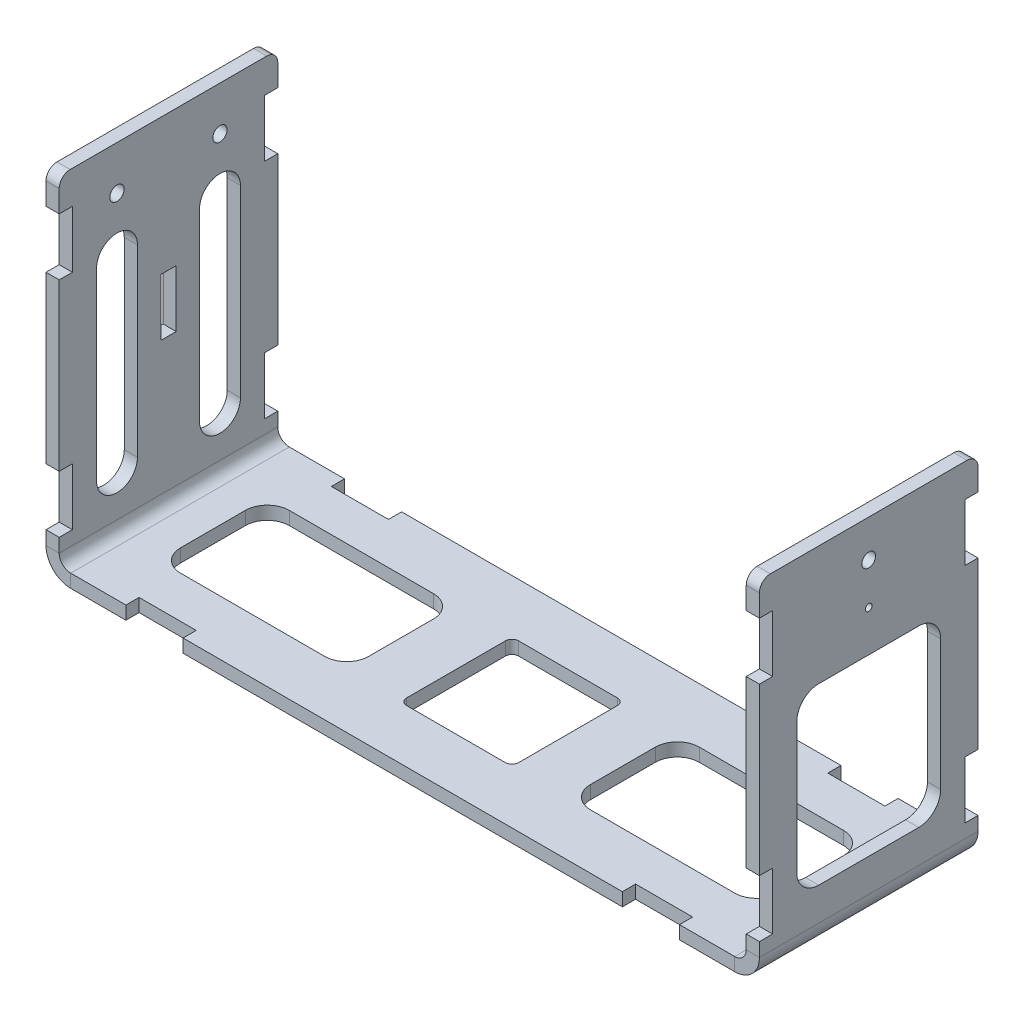
SolidWorks part; units mm, degrees
note: The reader was unsure of these and kept them because the rebuilt part matched: bend radius of "Base-Flange1", "BaseBend1", "BaseBend2".
ref_plane "Front Plane" through (0, 0, 0) normal (0, 0, 1) x (1, 0, 0)
ref_plane "Top Plane" through (0, 0, 0) normal (0, 1, 0) x (1, 0, 0)
ref_plane "Right Plane" through (0, 0, 0) normal (1, 0, 0) x (0, 0, -1)
sketch "Sketch1" plane through (0, 0, 0) normal (0, 0, 1) x (1, 0, 0)
  line L0 (79.4411, 0) -> (-79.4411, 0)
  line L1 (-79.4411, 0) -> (-79.4411, 78.232)
  line L2 (0, -1000) -> (0, 49000) construction
  line L3 (79.4411, 0) -> (79.4411, 78.232)
  line L4 (0, 78.232) -> (-38.1661, 40.0659) construction
  line L5 (-1000, 78.232) -> (49000, 78.232) construction
  line L6 (-66.7411, -930.7018) -> (-66.7411, 49069.2982) construction
  circle A0 centre (0, 78.232) radius 25.4 construction
  circle A1 centre (-38.1661, 40.0659) radius 28.575 construction
  circle A2 centre (0, 78.232) radius 29.21 construction
  point P7 (0, 0)
  dimension "D1" = 50.8
  dimension "D2" = 57.15
  dimension "D4" = 45
  dimension "D6" = 12.7
base flange "Base-Flange1" sketch "Sketch1" end condition mid plane depth 50.546 reverse direction no thickness 3.048 reverse thickness direction yes bend radius 2.667
bend "BaseBend1" bend radius 2.667 bend angle 90 parameters "D5"=1
bend "BaseBend2" bend radius 2.667 bend angle 90 parameters "D5"=2
sketch "Sketch6" plane through (0, 0, 0) normal (0, 1, 0) x (1, 0, 0)
  line L0 (76.7741, 25.273) -> (-76.7741, 25.273) construction
  line L1 (-64.008, 25.273) -> (-50.8, 25.273)
  line L2 (-64.008, 25.273) -> (-64.008, 22.225)
  line L3 (-64.008, 22.225) -> (-50.8, 22.225)
  line L4 (-50.8, 25.273) -> (-50.8, 22.225)
  line L5 (76.7741, -25.273) -> (-76.7741, -25.273) construction
  line L6 (-64.008, -25.273) -> (-50.8, -25.273)
  line L7 (-64.008, -25.273) -> (-64.008, -22.225)
  line L8 (-64.008, -22.225) -> (-50.8, -22.225)
  line L9 (-50.8, -25.273) -> (-50.8, -22.225)
  line L10 (-1000, 0) -> (49000, 0) construction
  line L11 (0, -1000) -> (0, 49000) construction
  line L24 (50.8, -25.273) -> (50.8, -22.225)
  line L25 (64.008, -22.225) -> (50.8, -22.225)
  line L26 (64.008, -25.273) -> (64.008, -22.225)
  line L27 (64.008, -25.273) -> (50.8, -25.273)
  line L28 (50.8, 25.273) -> (50.8, 22.225)
  line L29 (64.008, 22.225) -> (50.8, 22.225)
  line L30 (64.008, 25.273) -> (64.008, 22.225)
  line L31 (64.008, 25.273) -> (50.8, 25.273)
  dimension "D1" = 13.208
  dimension "D2" = 3.048
  dimension "D3" = 50.8
extrude "Cut-Extrude1" cut sketch "Sketch6" against normal through all both and the other way through all normal cut yes
sketch "Sketch7" plane through (-79.4411, 0, 0) normal (1, 0, 0) x (0, 0, -1)
  line L0 (-25.273, 78.232) -> (-25.273, 2.667) construction
  line L1 (-25.273, 19.05) -> (-22.225, 19.05)
  line L2 (-25.273, 19.05) -> (-25.273, 5.842)
  line L3 (-25.273, 5.842) -> (-22.225, 5.842)
  line L4 (-22.225, 19.05) -> (-22.225, 5.842)
  line L5 (-25.273, -3.048) -> (25.273, -3.048) construction
  line L6 (0, -1000) -> (0, 49000) construction
  line L7 (22.225, 19.05) -> (22.225, 5.842)
  line L8 (25.273, 5.842) -> (22.225, 5.842)
  line L9 (25.273, 19.05) -> (25.273, 5.842)
  line L10 (25.273, 19.05) -> (22.225, 19.05)
  line L11 (-1000, 38.227) -> (49000, 38.227) construction
  line L12 (25.273, 57.404) -> (22.225, 57.404)
  line L13 (25.273, 57.404) -> (25.273, 70.612)
  line L14 (25.273, 70.612) -> (22.225, 70.612)
  line L15 (22.225, 57.404) -> (22.225, 70.612)
  line L16 (-22.225, 57.404) -> (-22.225, 70.612)
  line L17 (-25.273, 70.612) -> (-22.225, 70.612)
  line L18 (-25.273, 57.404) -> (-25.273, 70.612)
  line L19 (-25.273, 57.404) -> (-22.225, 57.404)
  line L20 (-25.273, 78.232) -> (25.273, 78.232) construction
  point P25 (23.749, 70.612)
  dimension "D1" = 13.208
  dimension "D2" = 3.048
  dimension "D3" = 8.89
  dimension "D4" = 7.62
extrude "Cut-Extrude2" cut sketch "Sketch7" against normal through all both and the other way through all normal cut yes
fillet "Fillet1" radius 2.54 4 edges at (80.9651, 78.232, -25.273) (80.9651, 78.232, 25.273) (-80.9651, 78.232, -25.273) (-80.9651, 78.232, 25.273)
sketch "Sketch8" plane through (79.4411, 0, 0) normal (-1, 0, 0) x (0, 0, 1)
  circle A11 centre (0, 58.2504) radius 0.7747
  circle A12 centre (0, 58.2504) radius 0.7747
  circle A14 centre (0, 70.9504) radius 0.7747
  circle A15 centre (0, 70.9504) radius 0.7747
  dimension "D1" = 1.016
  dimension "D2" = 1.016
extrude "Cut-Extrude3" [suppressed] cut sketch "Sketch8" against normal through all
sketch "Sketch9" plane through (79.4411, 0, 0) normal (-1, 0, 0) x (0, 0, 1)
  circle A0 centre (0, 69.6386) radius 1.5875 construction
  circle A1 centre (0, 69.6386) radius 1.5875
  circle A4 centre (0, 60.1136) radius 0.7747
  circle A5 centre (0, 60.1136) radius 0.7747
  dimension "D1" = 1.016
extrude "Cut-Extrude4" cut sketch "Sketch9" against normal through all normal cut yes
sketch "Sketch10" plane through (-82.4891, 0, 0) normal (-1, 0, 0) x (0, 0, 1)
  circle A5 centre (11.9062, 68.072) radius 1.651
  circle A6 centre (11.9062, 68.072) radius 1.651
  circle A8 centre (-11.9063, 68.072) radius 1.651
  circle A9 centre (-11.9063, 68.072) radius 1.651
  dimension "D1" = 1.524
  dimension "D2" = 1.524
extrude "Cut-Extrude5" cut sketch "Sketch10" against normal up to next normal cut yes
sketch "Sketch11" plane through (-82.4891, 0, 0) normal (-1, 0, 0) x (0, 0, 1)
  line L0 (0, -925.366) -> (0, 49074.634) construction
  line L1 (-25.273, 19.05) -> (-25.273, 57.404) construction
  line L2 (25.273, 19.05) -> (25.273, 57.404) construction
  line L3 (22.733, 78.232) -> (-22.733, 78.232) construction
  line L4 (1.778, 33.528) -> (-1.778, 33.528)
  line L5 (1.778, 33.528) -> (1.778, 46.736)
  line L6 (1.778, 46.736) -> (-1.778, 46.736)
  line L7 (-1.778, 33.528) -> (-1.778, 46.736)
  line L8 (1.778, 33.528) -> (-1.778, 46.736) construction
  line L9 (1.778, 46.736) -> (-1.778, 33.528) construction
  point P6 (0, 40.132)
  dimension "D1" = 3.556
  dimension "D2" = 13.208
  dimension "D3" = 38.1
extrude "Cut-Extrude6" cut sketch "Sketch11" against normal up to next normal cut yes
sketch "Sketch13" plane through (82.4891, 0, 0) normal (1, 0, 0) x (0, 0, -1)
  line L0 (0, 44.8736) -> (0, 17.907) construction
  line L1 (10.033, 44.8736) -> (10.033, 17.907)
  line L2 (-10.033, 44.8736) -> (-10.033, 17.907)
  line L3 (-25.273, 57.404) -> (-25.273, 19.05) construction
  line L4 (-25.273, 2.667) -> (25.273, 2.667) construction
  arc A0 (10.033, 44.8736) -> (-10.033, 44.8736) centre (0, 44.8736) ccw
  arc A1 (-10.033, 17.907) -> (10.033, 17.907) centre (0, 17.907) ccw
  circle A2 centre (0, 60.1136) radius 0.7747 construction
  point P3 (0, 31.3903)
  dimension "D1" = 15.24
  dimension "D2" = 15.24
  dimension "D3" = 15.24
extrude "Cut-Extrude7" [suppressed] cut sketch "Sketch13" against normal up to next
sketch "Sketch14" plane through (0, 0, 0) normal (0, 1, 0) x (1, 0, 0)
  line L1 (-15.875, 25.273) -> (15.875, 25.273) construction
  line L2 (-15.875, 25.273) -> (-15.875, -25.273) construction
  line L3 (-15.875, -25.273) -> (15.875, -25.273) construction
  line L4 (15.875, 25.273) -> (15.875, -25.273) construction
  line L6 (50.8, 25.273) -> (-50.8, 25.273) construction
  line L7 (50.8, -25.273) -> (-50.8, -25.273) construction
  point P6 (0, 25.273)
  dimension "D1" = 31.75
sketch "Sketch15" plane through (0, -3.048, 0) normal (0, -1, 0) x (1, 0, 0)
  line L0 (-1000, 0) -> (49000, 0) construction
  line L1 (50.8, 25.273) -> (-50.8, 25.273) construction
  line L6 (-69.1541, 12.573) -> (-25.654, 12.573)
  line L7 (-69.1541, 12.573) -> (-69.1541, -12.573)
  line L12 (-69.1541, -12.573) -> (-25.654, -12.573)
  line L13 (-25.654, 12.573) -> (-25.654, -12.573)
  line L14 (-76.7741, 25.273) -> (-76.7741, -25.273) construction
  line L15 (0, -1000) -> (0, 49000) construction
  line L16 (25.654, 12.573) -> (25.654, -12.573)
  line L17 (69.1541, -12.573) -> (25.654, -12.573)
  line L18 (69.1541, 12.573) -> (69.1541, -12.573)
  line L19 (69.1541, 12.573) -> (25.654, 12.573)
  line L34 (12.954, -11.43) -> (12.954, 11.43)
  line L35 (-11.43, -12.954) -> (11.43, -12.954)
  line L36 (-12.954, 11.43) -> (-12.954, -11.43)
  line L37 (11.43, 12.954) -> (-11.43, 12.954)
  line L38 (12.954, -11.43) -> (12.954, 11.43)
  line L39 (-11.43, -12.954) -> (11.43, -12.954)
  line L40 (-12.954, 11.43) -> (-12.954, -11.43)
  line L41 (11.43, 12.954) -> (-11.43, 12.954)
  arc A20 (12.954, 11.43) -> (11.43, 12.954) centre (11.43, 11.43) ccw
  arc A21 (11.43, -12.954) -> (12.954, -11.43) centre (11.43, -11.43) ccw
  arc A22 (-12.954, -11.43) -> (-11.43, -12.954) centre (-11.43, -11.43) ccw
  arc A23 (-11.43, 12.954) -> (-12.954, 11.43) centre (-11.43, 11.43) ccw
  arc A24 (12.954, 11.43) -> (11.43, 12.954) centre (11.43, 11.43) ccw
  arc A25 (11.43, -12.954) -> (12.954, -11.43) centre (11.43, -11.43) ccw
  arc A26 (-12.954, -11.43) -> (-11.43, -12.954) centre (-11.43, -11.43) ccw
  arc A27 (-11.43, 12.954) -> (-12.954, 11.43) centre (-11.43, 11.43) ccw
  dimension "D1" = 0.254
  dimension "D2" = 12.7
  dimension "D3" = 12.7
  dimension "D4" = 7.62
extrude "Cut-Extrude8" cut sketch "Sketch15" against normal up to next normal cut yes
fillet "Fillet2" radius 5.08 8 edges at (-69.1541, -1.524, -12.573) (-25.654, -1.524, -12.573) (69.1541, -1.524, -12.573) (25.654, -1.524, -12.573) (25.654, -1.524, 12.573) (69.1541, -1.524, 12.573) (-25.654, -1.524, 12.573) (-69.1541, -1.524, 12.573)
sketch "Sketch17" plane through (-82.4891, 0, 0) normal (-1, 0, 0) x (0, 0, 1)
  line L0 (0, -953.264) -> (0, 49046.736) construction
  line L1 (1.778, 46.736) -> (-1.778, 46.736) construction
  line L2 (-11.9063, 55.372) -> (-11.9063, 12.827) construction
  line L3 (-7.1755, 55.372) -> (-7.1755, 12.827)
  line L4 (-16.637, 55.372) -> (-16.637, 12.827)
  line L5 (-11.9062, -931.928) -> (-11.9063, 49068.072) construction
  line L6 (-22.225, 70.612) -> (-22.225, 57.404) construction
  line L7 (25.273, 2.667) -> (-25.273, 2.667) construction
  line L8 (11.9062, 55.372) -> (11.9063, 12.827) construction
  line L9 (7.1755, 55.372) -> (7.1755, 12.827)
  line L10 (16.637, 55.372) -> (16.637, 12.827)
  arc A0 (-7.1755, 55.372) -> (-16.637, 55.372) centre (-11.9063, 55.372) ccw
  arc A1 (-16.637, 12.827) -> (-7.1755, 12.827) centre (-11.9063, 12.827) ccw
  circle A3 centre (-11.9063, 68.072) radius 1.651 construction
  arc A4 (7.1755, 55.372) -> (16.637, 55.372) centre (11.9062, 55.372) cw
  arc A5 (16.637, 12.827) -> (7.1755, 12.827) centre (11.9063, 12.827) cw
  point P5 (0, 46.736)
  point P7 (-11.9063, 34.0995)
  point P23 (11.9063, 34.0995)
  dimension "D1" = 12.7
  dimension "D2" = 5.588
  dimension "D3" = 10.16
extrude "Cut-Extrude9" cut sketch "Sketch17" against normal up to next normal cut yes
sketch "Sketch19" plane through (0, -3.048, 0) normal (0, -1, 0) x (1, 0, 0)
  line L0 (-1000, 0) -> (49000, 0) construction
  line L1 (-66.6141, 16.637) -> (66.6141, 16.637)
  line L2 (-66.6141, 16.637) -> (-66.6141, -16.637)
  line L3 (-66.6141, -16.637) -> (66.6141, -16.637)
  line L4 (66.6141, 16.637) -> (66.6141, -16.637)
  line L5 (-50.8, 22.225) -> (-64.008, 22.225) construction
  line L6 (-76.7741, 25.273) -> (-76.7741, -25.273) construction
  line L7 (76.7741, 25.273) -> (76.7741, -25.273) construction
  dimension "D1" = 5.588
  dimension "D2" = 10.16
  dimension "D3" = 10.16
extrude "Cut-Extrude10" [suppressed] cut sketch "Sketch19" against normal up to next
fillet "Fillet3" [suppressed] radius 5.08
sketch "Sketch20" plane through (-82.4891, 0, 0) normal (-1, 0, 0) x (0, 0, 1)
  line L0 (0, -1000) -> (0, 49000) construction
  line L1 (11.9062, 12.827) -> (11.9062, 55.372) construction
  line L2 (8.4931, 12.827) -> (8.4931, 55.372)
  line L3 (15.3194, 12.827) -> (15.3194, 55.372)
  line L4 (11.9063, -931.928) -> (11.9062, 49068.072) construction
  line L5 (25.273, 2.667) -> (-25.273, 2.667) construction
  line L6 (0, 12.827) -> (0, 55.372) construction
  line L7 (-3.4131, 12.827) -> (-3.4131, 55.372)
  line L8 (3.4131, 12.827) -> (3.4131, 55.372)
  line L9 (-11.9063, 12.827) -> (-11.9063, 55.372) construction
  line L10 (-8.4931, 12.827) -> (-8.4931, 55.372)
  line L11 (-15.3194, 12.827) -> (-15.3194, 55.372)
  arc A0 (8.4931, 12.827) -> (15.3194, 12.827) centre (11.9062, 12.827) ccw
  arc A1 (15.3194, 55.372) -> (8.4931, 55.372) centre (11.9062, 55.372) ccw
  arc A2 (-3.4131, 12.827) -> (3.4131, 12.827) centre (0, 12.827) ccw
  arc A3 (3.4131, 55.372) -> (-3.4131, 55.372) centre (0, 55.372) ccw
  arc A4 (-8.4931, 12.827) -> (-15.3194, 12.827) centre (-11.9063, 12.827) cw
  arc A5 (-15.3194, 55.372) -> (-8.4931, 55.372) centre (-11.9063, 55.372) cw
  point P5 (11.9062, 34.0995)
  point P17 (0, 34.0995)
  point P27 (-11.9063, 34.0995)
  dimension "D1" = 10.16
  dimension "D2" = 12.7
  dimension "D3" = 5.08
extrude "Cut-Extrude11" [suppressed] cut sketch "Sketch20" against normal up to next
sketch "Sketch21" plane through (82.4891, 0, 0) normal (1, 0, 0) x (0, 0, -1)
  line L0 (0, -997.333) -> (0, 49002.667) construction
  line L1 (16.637, 10.287) -> (-16.637, 10.287)
  line L2 (16.637, 10.287) -> (16.637, 50.6304)
  line L3 (16.637, 50.6304) -> (-16.637, 50.6304)
  line L4 (-16.637, 10.287) -> (-16.637, 50.6304)
  line L5 (-25.273, 2.667) -> (25.273, 2.667) construction
  line L6 (-22.225, 5.842) -> (-22.225, 19.05) construction
  point P9 (0, 2.667)
  dimension "D1" = 7.62
  dimension "D2" = 7.62
  dimension "D3" = 5.588
extrude "Cut-Extrude12" cut sketch "Sketch21" against normal up to next normal cut yes
fillet "Fillet4" radius 5.08 4 edges at (80.9651, 10.287, 16.637) (80.9651, 50.6304, -16.637) (80.9651, 50.6304, 16.637) (80.9651, 10.287, -16.637)
sketch "Bend-Lines1" [suppressed] plane through (0, 0, 0) normal (0, 1, 0) x (1, 0, 0)
sketch "Bounding-Box1" [suppressed] plane through (0, 0, 0) normal (0, 1, 0) x (1, 0, 0)
sheet metal parameters "Sheet-Metal1" thickness 3.048 parameters "D1"=2.667
flat pattern "Flat-Pattern1" [suppressed]
sketch "Bend-Lines2" plane through (0, -3.048, 0) normal (0, -1, 0) x (-1, 0, 0)
  line L0 (-98.0262, -38.1) -> (-98.0262, 38.1) construction
  line L1 (98.0262, 38.1) -> (98.0262, -38.1) construction
  line L2 (-98.0262, -38.1) -> (-98.0262, 38.1) construction
  line L3 (98.0262, 38.1) -> (98.0262, -38.1) construction
sketch3d "Bounding-Box2" [suppressed]
  line L0 (-97.7692, 76.2, 0) -> (292.5724, 76.2, 0) construction
  line L1 (-97.7692, 0, 0) -> (292.5724, 0, 0) construction
  line L2 (-97.7692, 76.2, 0) -> (-97.7692, 0, 0) construction
  line L3 (292.5724, 76.2, 0) -> (292.5724, 0, 0) construction
bend of the flat pattern "Flatten-<BaseBend1>1"
bend of the flat pattern "Flatten-<BaseBend2>1"
sheet metal parameters "Sheet-Metal2" thickness 3.048 parameters "D1"=2.667
flat pattern "Flat-Pattern1"
sketch "Bend-Lines2" plane through (0, -3.048, 0) normal (0, -1, 0) x (-1, 0, 0)
  line L0 (-98.0262, -38.1) -> (-98.0262, 38.1) construction
  line L1 (98.0262, 38.1) -> (98.0262, -38.1) construction
  line L2 (-98.0262, -38.1) -> (-98.0262, 38.1) construction
  line L3 (98.0262, 38.1) -> (98.0262, -38.1) construction
sketch3d "Bounding-Box2" [suppressed]
  line L0 (-97.7692, 76.2, 0) -> (292.5724, 76.2, 0) construction
  line L1 (-97.7692, 0, 0) -> (292.5724, 0, 0) construction
  line L2 (-97.7692, 76.2, 0) -> (-97.7692, 0, 0) construction
  line L3 (292.5724, 76.2, 0) -> (292.5724, 0, 0) construction
bend of the flat pattern "Flatten-<BaseBend1>1"
bend of the flat pattern "Flatten-<BaseBend2>1"
sheet metal parameters "Sheet-Metal3" thickness 3.048 parameters "D1"=2.667
flat pattern "Flat-Pattern1"
sketch "Bend-Lines2" plane through (0, -3.048, 0) normal (0, -1, 0) x (-1, 0, 0)
  line L0 (-98.0262, -25.273) -> (-98.0262, 25.273) construction
  line L1 (98.0262, 25.273) -> (98.0262, -25.273) construction
  line L2 (-98.0262, -25.273) -> (-98.0262, 25.273) construction
  line L3 (98.0262, 25.273) -> (98.0262, -25.273) construction
sketch3d "Bounding-Box2" [suppressed]
  line L0 (-108.7135, 50.546, 0) -> (303.5167, 50.546, 0) construction
  line L1 (-108.7135, 0, 0) -> (303.5167, 0, 0) construction
  line L2 (-108.7135, 50.546, 0) -> (-108.7135, 0, 0) construction
  line L3 (303.5167, 50.546, 0) -> (303.5167, 0, 0) construction
bend of the flat pattern "Flatten-<BaseBend1>1"
bend of the flat pattern "Flatten-<BaseBend2>1"
sheet metal parameters "Sheet-Metal4" thickness 3.048 parameters "D1"=2.667
flat pattern "Flat-Pattern1"
sketch "Bend-Lines2" plane through (0, -3.048, 0) normal (0, -1, 0) x (-1, 0, 0)
  line L0 (-98.0262, -25.273) -> (-98.0262, 25.273) construction
  line L1 (98.0262, 25.273) -> (98.0262, -25.273) construction
  line L2 (-98.0262, -25.273) -> (-98.0262, 25.273) construction
  line L3 (98.0262, 25.273) -> (98.0262, -25.273) construction
sketch3d "Bounding-Box2" [suppressed]
  line L0 (-108.7135, 50.546, 0) -> (303.5167, 50.546, 0) construction
  line L1 (-108.7135, 0, 0) -> (303.5167, 0, 0) construction
  line L2 (-108.7135, 50.546, 0) -> (-108.7135, 0, 0) construction
  line L3 (303.5167, 50.546, 0) -> (303.5167, 0, 0) construction
bend of the flat pattern "Flatten-<BaseBend1>1"
bend of the flat pattern "Flatten-<BaseBend2>1"
sheet metal parameters "Sheet-Metal5" thickness 3.048 parameters "D1"=2.667
flat pattern "Flat-Pattern1"
sketch "Bend-Lines2" plane through (0, -3.048, 0) normal (0, -1, 0) x (-1, 0, 0)
  line L0 (-98.0262, -25.273) -> (-98.0262, 25.273) construction
  line L1 (98.0262, 25.273) -> (98.0262, -25.273) construction
  line L2 (-98.0262, -25.273) -> (-98.0262, 25.273) construction
  line L3 (98.0262, 25.273) -> (98.0262, -25.273) construction
sketch3d "Bounding-Box2" [suppressed]
  line L0 (-108.7135, 50.546, 0) -> (303.5167, 50.546, 0) construction
  line L1 (-108.7135, 0, 0) -> (303.5167, 0, 0) construction
  line L2 (-108.7135, 50.546, 0) -> (-108.7135, 0, 0) construction
  line L3 (303.5167, 50.546, 0) -> (303.5167, 0, 0) construction
bend of the flat pattern "Flatten-<BaseBend1>1"
bend of the flat pattern "Flatten-<BaseBend2>1"
sheet metal parameters "Sheet-Metal6" thickness 3.048 parameters "D1"=2.667
flat pattern "Flat-Pattern1"
sketch "Bend-Lines2" plane through (0, -3.048, 0) normal (0, -1, 0) x (-1, 0, 0)
  line L0 (-80.0657, -25.273) -> (-80.0657, 25.273) construction
  line L1 (80.0657, 25.273) -> (80.0657, -25.273) construction
  line L2 (-80.0657, -25.273) -> (-80.0657, 25.273) construction
  line L3 (80.0657, 25.273) -> (80.0657, -25.273) construction
sketch3d "Bounding-Box2" [suppressed]
  line L0 (-79.4812, 50.546, 0) -> (238.3634, 50.546, 0) construction
  line L1 (-79.4812, 0, 0) -> (238.3634, 0, 0) construction
  line L2 (-79.4812, 50.546, 0) -> (-79.4812, 0, 0) construction
  line L3 (238.3634, 50.546, 0) -> (238.3634, 0, 0) construction
bend of the flat pattern "Flatten-<BaseBend1>1"
bend of the flat pattern "Flatten-<BaseBend2>1"
sheet metal parameters "Sheet-Metal7" thickness 3.048 parameters "D1"=2.667
flat pattern "Flat-Pattern1"
sketch "Bend-Lines2" plane through (0, -3.048, 0) normal (0, -1, 0) x (-1, 0, 0)
  line L0 (-80.0657, -25.273) -> (-80.0657, 25.273) construction
  line L1 (80.0657, 25.273) -> (80.0657, -25.273) construction
  line L2 (-80.0657, -25.273) -> (-80.0657, 25.273) construction
  line L3 (80.0657, 25.273) -> (80.0657, -25.273) construction
sketch3d "Bounding-Box2" [suppressed]
  line L0 (-79.4812, 50.546, 0) -> (238.3634, 50.546, 0) construction
  line L1 (-79.4812, 0, 0) -> (238.3634, 0, 0) construction
  line L2 (-79.4812, 50.546, 0) -> (-79.4812, 0, 0) construction
  line L3 (238.3634, 50.546, 0) -> (238.3634, 0, 0) construction
bend of the flat pattern "Flatten-<BaseBend1>1"
bend of the flat pattern "Flatten-<BaseBend2>1"
sheet metal parameters "Sheet-Metal8" thickness 3.048 parameters "D1"=2.667
flat pattern "Flat-Pattern1"
sketch "Bend-Lines2" plane through (0, -3.048, 0) normal (0, -1, 0) x (-1, 0, 0)
  line L0 (-80.0657, -25.273) -> (-80.0657, 25.273) construction
  line L1 (80.0657, 25.273) -> (80.0657, -25.273) construction
  line L2 (-80.0657, -25.273) -> (-80.0657, 25.273) construction
  line L3 (80.0657, 25.273) -> (80.0657, -25.273) construction
sketch3d "Bounding-Box2" [suppressed]
  line L0 (-79.4812, 50.546, 0) -> (238.3634, 50.546, 0) construction
  line L1 (-79.4812, 0, 0) -> (238.3634, 0, 0) construction
  line L2 (-79.4812, 50.546, 0) -> (-79.4812, 0, 0) construction
  line L3 (238.3634, 50.546, 0) -> (238.3634, 0, 0) construction
bend of the flat pattern "Flatten-<BaseBend1>1"
bend of the flat pattern "Flatten-<BaseBend2>1"
sheet metal parameters "Sheet-Metal9" thickness 3.048 parameters "D1"=2.667
flat pattern "Flat-Pattern1"
sketch "Bend-Lines2" plane through (0, -3.048, 0) normal (0, -1, 0) x (-1, 0, 0)
  line L0 (-80.0657, -25.273) -> (-80.0657, 25.273) construction
  line L1 (80.0657, 25.273) -> (80.0657, -25.273) construction
  line L2 (-80.0657, -25.273) -> (-80.0657, 25.273) construction
  line L3 (80.0657, 25.273) -> (80.0657, -25.273) construction
sketch3d "Bounding-Box2" [suppressed]
  line L0 (-79.4812, 50.546, 0) -> (238.3634, 50.546, 0) construction
  line L1 (-79.4812, 0, 0) -> (238.3634, 0, 0) construction
  line L2 (-79.4812, 50.546, 0) -> (-79.4812, 0, 0) construction
  line L3 (238.3634, 50.546, 0) -> (238.3634, 0, 0) construction
bend of the flat pattern "Flatten-<BaseBend1>1"
bend of the flat pattern "Flatten-<BaseBend2>1"
sheet metal parameters "Sheet-Metal10" thickness 3.048 parameters "D1"=2.667
flat pattern "Flat-Pattern1"
sketch "Bend-Lines2" plane through (0, -3.048, 0) normal (0, -1, 0) x (-1, 0, 0)
  line L0 (-80.0657, -25.273) -> (-80.0657, 25.273) construction
  line L1 (80.0657, 25.273) -> (80.0657, -25.273) construction
  line L2 (-80.0657, -25.273) -> (-80.0657, 25.273) construction
  line L3 (80.0657, 25.273) -> (80.0657, -25.273) construction
sketch3d "Bounding-Box2" [suppressed]
  line L0 (-79.4812, 50.546, 0) -> (238.3634, 50.546, 0) construction
  line L1 (-79.4812, 0, 0) -> (238.3634, 0, 0) construction
  line L2 (-79.4812, 50.546, 0) -> (-79.4812, 0, 0) construction
  line L3 (238.3634, 50.546, 0) -> (238.3634, 0, 0) construction
bend of the flat pattern "Flatten-<BaseBend1>1"
bend of the flat pattern "Flatten-<BaseBend2>1"
sheet metal parameters "Sheet-Metal11" thickness 3.048 parameters "D1"=2.667
flat pattern "Flat-Pattern1"
sketch "Bend-Lines2" plane through (0, -3.048, 0) normal (0, -1, 0) x (-1, 0, 0)
  line L0 (-80.0657, -25.273) -> (-80.0657, 25.273) construction
  line L1 (80.0657, 25.273) -> (80.0657, -25.273) construction
  line L2 (-80.0657, -25.273) -> (-80.0657, 25.273) construction
  line L3 (80.0657, 25.273) -> (80.0657, -25.273) construction
sketch3d "Bounding-Box2" [suppressed]
  line L0 (-79.4812, 50.546, 0) -> (238.3634, 50.546, 0) construction
  line L1 (-79.4812, 0, 0) -> (238.3634, 0, 0) construction
  line L2 (-79.4812, 50.546, 0) -> (-79.4812, 0, 0) construction
  line L3 (238.3634, 50.546, 0) -> (238.3634, 0, 0) construction
bend of the flat pattern "Flatten-<BaseBend1>1"
bend of the flat pattern "Flatten-<BaseBend2>1"
sheet metal parameters "Sheet-Metal12" thickness 3.048 parameters "D1"=2.667
flat pattern "Flat-Pattern1"
sketch "Bend-Lines2" plane through (0, -3.048, 0) normal (0, -1, 0) x (-1, 0, 0)
  line L0 (-80.0657, -25.273) -> (-80.0657, 25.273) construction
  line L1 (80.0657, 25.273) -> (80.0657, -25.273) construction
  line L2 (-80.0657, -25.273) -> (-80.0657, 25.273) construction
  line L3 (80.0657, 25.273) -> (80.0657, -25.273) construction
sketch3d "Bounding-Box2" [suppressed]
  line L0 (-79.4812, 50.546, 0) -> (238.3634, 50.546, 0) construction
  line L1 (-79.4812, 0, 0) -> (238.3634, 0, 0) construction
  line L2 (-79.4812, 50.546, 0) -> (-79.4812, 0, 0) construction
  line L3 (238.3634, 50.546, 0) -> (238.3634, 0, 0) construction
bend of the flat pattern "Flatten-<BaseBend1>1"
bend of the flat pattern "Flatten-<BaseBend2>1"
sheet metal parameters "Sheet-Metal13" thickness 3.048 parameters "D1"=2.667
flat pattern "Flat-Pattern1"
sketch "Bend-Lines2" plane through (0, -3.048, 0) normal (0, -1, 0) x (-1, 0, 0)
  line L0 (-80.0657, -25.273) -> (-80.0657, 25.273) construction
  line L1 (80.0657, 25.273) -> (80.0657, -25.273) construction
  line L2 (-80.0657, -25.273) -> (-80.0657, 25.273) construction
  line L3 (80.0657, 25.273) -> (80.0657, -25.273) construction
sketch3d "Bounding-Box2" [suppressed]
  line L0 (-79.4812, 50.546, 0) -> (238.3634, 50.546, 0) construction
  line L1 (-79.4812, 0, 0) -> (238.3634, 0, 0) construction
  line L2 (-79.4812, 50.546, 0) -> (-79.4812, 0, 0) construction
  line L3 (238.3634, 50.546, 0) -> (238.3634, 0, 0) construction
bend of the flat pattern "Flatten-<BaseBend1>1"
bend of the flat pattern "Flatten-<BaseBend2>1"
equation "\"D2@Base-Flange1\"=1.750000in + 0.24in"
equation "\"D2@Sketch13\"=\"D1@Sketch13\""
equation "\"D3@Sketch13\"=\"D1@Sketch13\""
